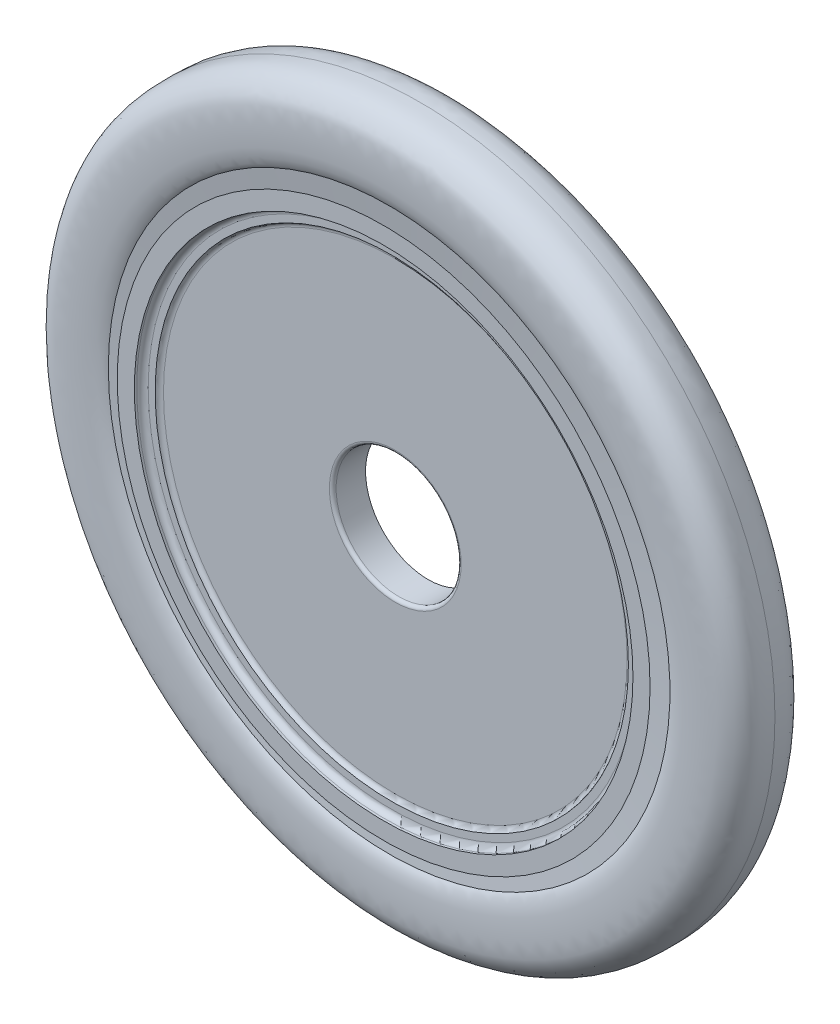
SolidWorks part; units mm, degrees
ref_plane "Front" through (0, 0, 0) normal (0, 0, 1) x (1, 0, 0)
ref_plane "Top" through (0, 0, 0) normal (0, 1, 0) x (1, 0, 0)
ref_plane "Right" through (0, 0, 0) normal (1, 0, 0) x (0, 0, -1)
sketch "Sketch1" plane through (0, 0, 0) normal (0, 0, 1) x (1, 0, 0)
  circle A0 centre (0, 0) radius 279.4
  dimension "D1" = 558.8
extrude "Extrude1" add sketch "Sketch1" along normal blind 54.61
sketch "Sketch2" plane through (0, 0, 54.61) normal (0, 0, 1) x (1, 0, 0)
  circle A0 centre (0, 0) radius 46.99
  dimension "D1" = 93.98
extrude "Cut-Extrude1" cut sketch "Sketch2" against normal through all
sketch "Sketch3" plane through (0, 0, 54.61) normal (0, 0, 1) x (1, 0, 0)
  circle A0 centre (0, 0) radius 187.325
  dimension "D1" = 374.65
extrude "Cut-Extrude2" cut sketch "Sketch3" against normal blind 6.096
sketch "Sketch4" plane through (0, 0, 48.514) normal (0, 0, 1) x (1, 0, 0)
  circle A0 centre (0, 0) radius 177.8
  dimension "D1" = 355.6
extrude "Cut-Extrude3" cut sketch "Sketch4" against normal blind 2.6416
fillet "Fillet6" radius 3.81 1 edges at (177.8, 0, 45.8724)
fillet "Fillet7" radius 4.318 1 edges at (187.325, 0, 48.514)
fillet "Fillet8" radius 2.54 1 edges at (46.99, 0, 45.8724)
sketch "Sketch5" plane through (0, 0, 0) normal (0, 0, -1) x (-1, 0, 0)
  circle A0 centre (0, 0) radius 187.325
  dimension "D1" = 374.65
extrude "Cut-Extrude4" cut sketch "Sketch5" against normal blind 5.9944
fillet "Fillet9" radius 5.08 1 edges at (-187.325, 0, 5.9944)
sketch "Sketch6" plane through (0, 0, 5.9944) normal (0, 0, -1) x (-1, 0, 0)
  circle A0 centre (0, 0) radius 176.2125
  dimension "D1" = 352.425
extrude "Cut-Extrude5" cut sketch "Sketch6" against normal blind 9.3218
fillet "Fillet10" radius 6.35 1 edges at (-176.2125, 0, 5.9944)
ref_plane "hub contact surcafe" through (0, 0, 21.2344) normal (0, 0, 1) x (1, 0, 0)
sketch "Sketch7" plane through (0, 0, 21.2344) normal (0, 0, 1) x (1, 0, 0)
  circle A0 centre (0, 0) radius 76.2
  dimension "D1" = 152.4
extrude "Cut-Extrude6" cut sketch "Sketch7" against normal through all
ref_plane "thin web" through (0, 0, 44.0944) normal (0, 0, 1) x (1, 0, 0)
sketch "Sketch9" plane through (0, 0, 44.0944) normal (0, 0, 1) x (1, 0, 0)
  line L0 (0, 0) -> (0, 240) construction
  line L1 (-11.43, 74.1738) -> (-11.43, 159.5216)
  line L2 (11.43, 74.1738) -> (11.43, 159.5216)
  line L3 (69.9514, 27.1882) -> (143.8647, 69.8621)
  line L4 (58.5214, 46.9856) -> (132.4347, 89.6594)
  line L5 (58.5214, -46.9856) -> (132.4347, -89.6594)
  line L6 (69.9514, -27.1882) -> (143.8647, -69.8621)
  line L7 (-11.43, -74.1738) -> (-11.43, -159.5216)
  line L8 (11.43, -74.1738) -> (11.43, -159.5216)
  line L9 (-69.9514, -27.1882) -> (-143.8647, -69.8621)
  line L10 (-58.5214, -46.9856) -> (-132.4347, -89.6594)
  line L11 (-58.5214, 46.9856) -> (-132.4347, 89.6594)
  line L12 (-69.9514, 27.1882) -> (-143.8647, 69.8621)
  arc A0 (-66.4219, 18.5404) -> (-66.4219, -18.5404) centre (0, 0) ccw
  arc A1 (-49.2674, -48.2529) -> (-17.1545, -66.7933) centre (0, 0) ccw
  arc A2 (49.2674, 48.2529) -> (17.1545, 66.7933) centre (0, 0) ccw
  arc A3 (-19.9536, 167.0878) -> (-134.7255, 100.8242) centre (0, 0) ccw
  arc A4 (66.4219, -18.5404) -> (66.4219, 18.5404) centre (0, 0) ccw
  arc A5 (17.1545, -66.7933) -> (49.2674, -48.2529) centre (0, 0) ccw
  arc A6 (-17.1545, 66.7933) -> (-49.2674, 48.2529) centre (0, 0) ccw
  arc A7 (-154.6791, 66.2636) -> (-154.6791, -66.2636) centre (0, 0) ccw
  arc A8 (-134.7255, -100.8242) -> (-19.9536, -167.0878) centre (0, 0) ccw
  arc A9 (19.9536, -167.0878) -> (134.7255, -100.8242) centre (0, 0) ccw
  arc A10 (154.6791, -66.2636) -> (154.6791, 66.2636) centre (0, 0) ccw
  arc A11 (134.7255, 100.8242) -> (19.9536, 167.0878) centre (0, 0) ccw
  arc A12 (-11.43, 159.5216) -> (-19.9536, 167.0878) centre (-19.05, 159.5216) ccw
  arc A13 (-132.4347, 89.6594) -> (-134.7255, 100.8242) centre (-128.6247, 96.2586) cw
  arc A14 (-154.6791, 66.2636) -> (-143.8647, 69.8621) centre (-147.6747, 63.263) cw
  arc A15 (-143.8647, -69.8621) -> (-154.6791, -66.2636) centre (-147.6747, -63.263) cw
  arc A16 (-134.7255, -100.8242) -> (-132.4347, -89.6594) centre (-128.6247, -96.2586) cw
  arc A17 (-11.43, -159.5216) -> (-19.9536, -167.0878) centre (-19.05, -159.5216) cw
  arc A18 (19.9536, -167.0878) -> (11.43, -159.5216) centre (19.05, -159.5216) cw
  arc A19 (132.4347, -89.6594) -> (134.7255, -100.8242) centre (128.6247, -96.2586) cw
  arc A20 (154.6791, -66.2636) -> (143.8647, -69.8621) centre (147.6747, -63.263) cw
  arc A21 (154.6791, 66.2636) -> (143.8647, 69.8621) centre (147.6747, 63.263) ccw
  arc A22 (134.7255, 100.8242) -> (132.4347, 89.6594) centre (128.6247, 96.2586) cw
  arc A23 (11.43, 159.5216) -> (19.9536, 167.0878) centre (19.05, 159.5216) cw
  arc A24 (69.9514, 27.1882) -> (66.4219, 18.5404) centre (73.7614, 20.5891) ccw
  arc A25 (49.2674, 48.2529) -> (58.5214, 46.9856) centre (54.7114, 53.5847) ccw
  arc A26 (11.43, 74.1738) -> (17.1545, 66.7933) centre (19.05, 74.1738) ccw
  arc A27 (-17.1545, 66.7933) -> (-11.43, 74.1738) centre (-19.05, 74.1738) ccw
  arc A28 (-58.5214, 46.9856) -> (-49.2674, 48.2529) centre (-54.7114, 53.5847) ccw
  arc A29 (-66.4219, 18.5404) -> (-69.9514, 27.1882) centre (-73.7614, 20.5891) ccw
  arc A30 (-69.9514, -27.1882) -> (-66.4219, -18.5404) centre (-73.7614, -20.5891) ccw
  arc A31 (-49.2674, -48.2529) -> (-58.5214, -46.9856) centre (-54.7114, -53.5847) ccw
  arc A32 (-11.43, -74.1738) -> (-17.1545, -66.7933) centre (-19.05, -74.1738) ccw
  arc A33 (17.1545, -66.7933) -> (11.43, -74.1738) centre (19.05, -74.1738) ccw
  arc A34 (58.5214, -46.9856) -> (49.2674, -48.2529) centre (54.7114, -53.5847) ccw
  arc A35 (66.4219, -18.5404) -> (69.9514, -27.1882) centre (73.7614, -20.5891) ccw
  point P3 (-11.43, 167.8864)
  point P52 (11.43, 167.8864)
  point P59 (11.43, 68.0072)
  point P62 (-11.43, 68.0072)
  dimension "D2" = 137.922
  dimension "D3" = 336.55
  dimension "D4" = 7.62
  dimension "D1" = 22.86
extrude "Cut-Extrude7" cut sketch "Sketch9" against normal up to next
sketch "Sketch10" plane through (0, 0, 21.2344) normal (0, 0, -1) x (-1, 0, 0)
  circle A0 centre (0, 0) radius 68.9991
  circle A1 centre (0, 0) radius 159.9305
  dimension "D1" = 137.9982
extrude "Cut-Extrude8" cut sketch "Sketch10" against normal blind 3.3528
ref_axis "Axis1" through (0, 0, 11480.3367) along (0, 0, -1)
sketch "Sketch13" plane through (0, 0, 0) normal (1, 0, 0) x (0, 0, -1)
  line L0 (-24.5872, 68.9991) -> (-32.5628, 169.2664)
  line L1 (-32.5628, 169.2664) -> (37.5063, 169.2664)
  line L2 (-24.5872, 68.9991) -> (37.5063, 68.9991)
  line L9 (37.5063, 68.9991) -> (37.5063, 169.2664)
  line L11 (-44.0944, 159.5216) -> (-44.0944, 74.1738) construction
  line L12 (70, 0) -> (-130, 0) construction
  line L13 (-11480.3367, 0) -> (5397.0692, 0) construction
  dimension "D1" = 11.5316
  dimension "D2" = 100.584
revolve "Cut-Revolve3" cut sketch "Sketch13" angle 360 about L12
sketch "Sketch14" plane through (0, 0, 0) normal (1, 0, 0) x (0, 0, -1)
  line L0 (-27.305, 170) -> (-27.305, 270) construction
  line L1 (-54.61, 279.4) -> (-54.61, -279.4) construction
  line L2 (0, -279.4) -> (0, 279.4) construction
  line L3 (-0.0177, 225.0409) -> (-0.0177, 220.1533) construction
  line L4 (-52.7044, 190.7119) -> (-47.9419, 190.7119)
  line L5 (0, 279.4) -> (-54.61, 279.4) construction
  line L6 (-1.9056, 190.7119) -> (-6.6681, 190.7119)
  line L7 (-6.6681, 190.7119) -> (-4.121, 210.995)
  line L8 (-47.9419, 190.7119) -> (-50.489, 210.995)
  line L9 (-1.9056, 190.7119) -> (18.9332, 238.9891)
  line L10 (18.9332, 238.9891) -> (2.8781, 283.3976)
  line L11 (2.8781, 283.3976) -> (-55.6236, 283.3976)
  line L12 (-55.6236, 283.3976) -> (-66.1531, 257.5246)
  line L13 (-66.1531, 257.5246) -> (-52.7044, 190.7119)
  line L14 (129.127, 0) -> (-184.7998, 0) construction
  line L15 (-11480.3367, 0) -> (5397.0692, 0) construction
  spline S0 degree 3 poles (-4.121, 210.995) (-3.717, 211.5776) (-3.3129, 212.1603) (-2.5102, 213.6929) (-1.8393, 215.8441) (-1.2756, 217.9968) (-0.5627, 221.5025) (-0.3453, 223.8944) (-0.069, 229.1937) (-0.0177, 232.0657) (-0.0177, 239.0811) (-0.126, 243.049) (-0.7981, 249.6624) (-1.7657, 253.0256) (-4.6546, 257.8508) (-7.537, 261.5114) (-12.1972, 264.9462) (-16.7157, 266.3235) (-20.7359, 266.6019) (-23.8577, 266.7113) (-26.0599, 266.7041) (-27.305, 266.7) knots 0 0 0 0 0.028977 0.028977 0.071307 0.120462 0.120462 0.218453 0.218453 0.337934 0.337934 0.50302 0.50302 0.60347 0.644828 0.727549 0.788819 0.874449 0.912386 0.950466 1 1 1 1
  spline S1 degree 3 poles (-50.489, 210.995) (-50.893, 211.5776) (-51.2971, 212.1603) (-52.0998, 213.6929) (-52.7707, 215.8441) (-53.3344, 217.9968) (-54.0473, 221.5025) (-54.2647, 223.8944) (-54.541, 229.1937) (-54.5923, 232.0657) (-54.5923, 239.0811) (-54.484, 243.049) (-53.8119, 249.6624) (-52.8443, 253.0256) (-49.9554, 257.8508) (-47.073, 261.5114) (-42.4128, 264.9462) (-37.8943, 266.3235) (-33.8741, 266.6019) (-30.7523, 266.7113) (-28.5501, 266.7041) (-27.305, 266.7) knots 0 0 0 0 0.028977 0.028977 0.071307 0.120462 0.120462 0.218453 0.218453 0.337934 0.337934 0.50302 0.50302 0.60347 0.644828 0.727549 0.788819 0.874449 0.912386 0.950466 1 1 1 1
  point P6 (-0.0177, 235.0113)
  point P7 (-18.415, 280.5719)
  dimension "D1" = 266.7
  dimension "D2" = 8.89
  dimension "D3" = 1.1719
  dimension "D4" = 3.8862
  dimension "D5" = 4.7625
revolve "Cut-Revolve4" cut sketch "Sketch14" angle 360 about L14
sketch "Sketch15" plane through (0, 0, 0) normal (0, 0, 1) x (1, 0, 0)
  line L0 (0, 0) -> (0, -317.2622) construction
  line L1 (11.43, -159.5216) -> (11.43, -74.1738) construction
  line L2 (9.4996, -73.1731) -> (-9.4996, -73.1731)
  line L3 (9.4996, -73.1731) -> (9.4996, -121.4342)
  line L4 (9.4996, -121.4342) -> (-9.4996, -121.4342)
  line L5 (-9.4996, -73.1731) -> (-9.4996, -121.4342)
  line L6 (9.4996, -123.4662) -> (-9.4996, -123.4662)
  line L7 (9.4996, -123.4662) -> (9.4996, -167.3414)
  line L8 (9.4996, -167.3414) -> (-9.4996, -167.3414)
  line L9 (-9.4996, -123.4662) -> (-9.4996, -167.3414)
  dimension "D1" = 1.9304
  dimension "D2" = 2.032
extrude "Cut-Extrude9" cut sketch "Sketch15" along normal up to surface (44.0944 mm away) up to face at (55.2891, -95.7636, 44.0944)
fillet "Fillet11" radius 6.35 8 edges at (9.4996, -167.3414, 38.2628) (9.4996, -123.4662, 36.5216) (-9.4996, -123.4662, 36.5216) (-9.4996, -167.3414, 38.2628) (-9.4996, -121.4342, 36.441) (9.4996, -121.4342, 36.441) (-9.4996, -73.1731, 34.5312) (9.4996, -73.1731, 34.5312)
pattern_circular "CirPattern2" count 6 over 360 about axis through (0, 0, 11480.3367) along (0, 0, -1) of "Fillet11", "Cut-Extrude9"
sketch "Sketch16" plane through (0, 0, 21.2344) normal (0, 0, -1) x (-1, 0, 0)
  line L0 (10.7203, 48.3559) -> (14.3761, 64.8466)
  line L1 (36.5173, 33.462) -> (48.9707, 44.8734)
  line L2 (33.2105, 57.5223) -> (0, 0) construction
  line L3 (0, 68.9991) -> (0, 46.9773) construction
  arc A0 (36.5173, 33.462) -> (10.7203, 48.3559) centre (0, 0) ccw
  circle A1 centre (0, 0) radius 46.99 construction
  arc A2 (48.9707, 44.8734) -> (14.3761, 64.8466) centre (0, 0) ccw
  arc A3 (49.2674, 48.2529) -> (17.1545, 66.7933) centre (0, 0) ccw construction
  circle A4 centre (0, 57.9882) radius 4.7625
  arc A5 (16.4633, 67.0062) -> (-16.4633, 67.0062) centre (0, 0) ccw construction
  dimension "D1" = 2.54
  dimension "D2" = 2.54
  dimension "D3" = 9.525
  dimension "D4" = 57.9882
  dimension "D5" = 30
  dimension "D6" = 35
extrude "Cut-Extrude10" cut sketch "Sketch16" against normal up to surface (22.86 mm away) up to face at (-55.2891, 95.7636, 44.0944)
fillet "Fillet12" radius 6.35 4 edges at (-36.5173, 33.462, 32.6644) (-48.9707, 44.8734, 32.6644) (-14.3761, 64.8466, 32.6644) (-10.7203, 48.3559, 32.6644)
pattern_circular "CirPattern3" count 6 over 360 about axis through (0, 0, 11480.3367) along (0, 0, -1) of "Cut-Extrude10", "Fillet12"
